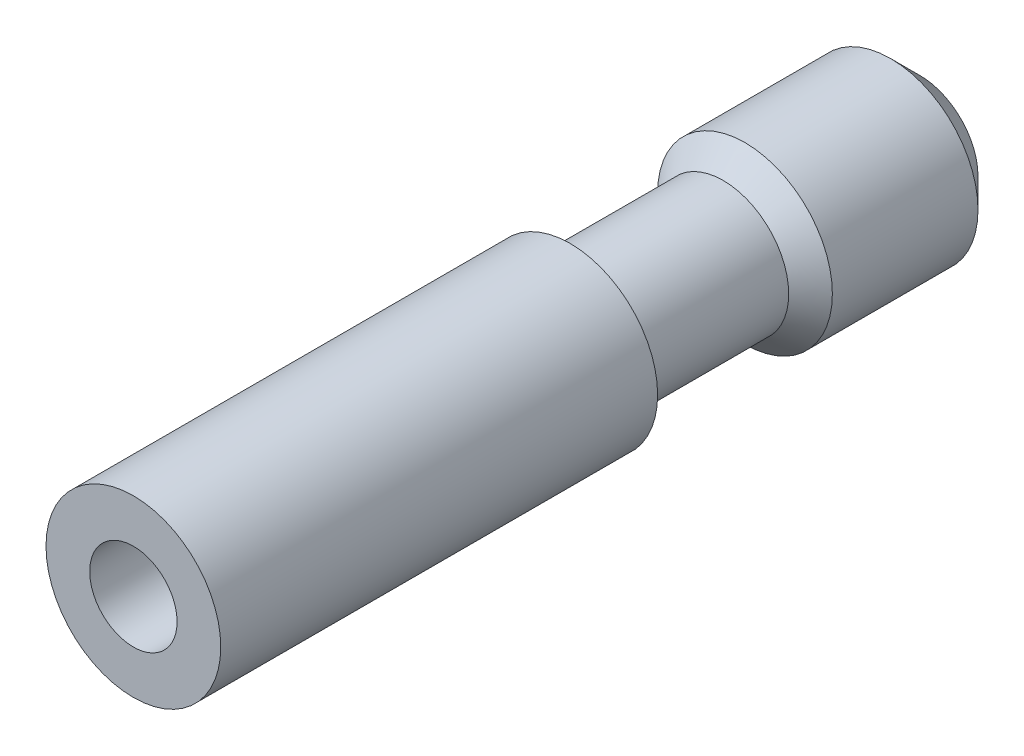
SolidWorks part; units mm, degrees
ref_plane "Plan de face" through (0, 0, 0) normal (0, 0, 1) x (1, 0, 0)
ref_plane "Plan de dessus" through (0, 0, 0) normal (0, 1, 0) x (1, 0, 0)
ref_plane "Plan de droite" through (0, 0, 0) normal (1, 0, 0) x (0, 0, -1)
sketch "Esquisse1" plane through (0, 0, 0) normal (0, 0, 1) x (1, 0, 0)
  circle A0 centre (0, 0) radius 3
  dimension "D1" = 6
extrude "Boss.-Extru.1" add sketch "Esquisse1" along normal blind 27 contours A0
cosmetic thread "Représentation de filetage1" parameters "D1"=5, "D2"=4.891
hole_wizard "Diamètre du perçage Ø3.0 (3)1" positions "Esquisse3" profile "Esquisse2" hole size "Ø3.0" standard "ISO"
sketch "Esquisse3" plane through (0, 0, 27) normal (0, 0, 1) x (1, 0, 0)
  point P0 (0, 0)
sketch "Esquisse2" plane through (0, 0, 27) normal (1, 0, 0) x (0, -1, 0)
  line L0 (0, 0) -> (0, 25.4013)
  line L1 (0, 25.4013) -> (1.5, 24.5)
  line L2 (1.5, 24.5) -> (1.5, 0)
  line L5 (1.5, 0) -> (0, 0)
  line L10 (0, 25.4013) -> (-1.5, 24.5) construction
  line L11 (0, -6.35) -> (0, 107.95) construction
  dimension "Diamètre du perçage" = 3
  dimension "Profondeur du perçage" = 24.5
  dimension "Angle de pointe" = 118
hole_wizard "Diamètre du perçage Ø2.5 (2.5)1" positions "Esquisse5" profile "Esquisse4" hole size "Ø2.5" standard "ISO"
sketch "Esquisse5" plane through (0, 0, 0) normal (0, 0, -1) x (-1, 0, 0)
  point P0 (0, 0)
sketch "Esquisse4" plane through (0, 0, 0) normal (1, 0, 0) x (0, 1, 0)
  line L0 (0, 0) -> (0, 3.7511)
  line L1 (0, 3.7511) -> (1.25, 3)
  line L2 (1.25, 3) -> (1.25, 0)
  line L5 (1.25, 0) -> (0, 0)
  line L10 (0, 3.7511) -> (-1.25, 3) construction
  line L11 (0, -6.35) -> (0, 107.95) construction
  dimension "Diamètre du perçage" = 2.5
  dimension "Profondeur du perçage" = 3
  dimension "Angle de pointe" = 118
sketch "Esquisse6" plane through (0, 0, 27) normal (0, 0, 1) x (1, 0, 0)
  line L1 (-6.0949, -5.2635) -> (5.6553, -5.2635)
  line L2 (-6.0949, -5.2635) -> (-6.0949, 6.1211)
  line L3 (-6.0949, 6.1211) -> (5.6553, 6.1211)
  line L4 (5.6553, -5.2635) -> (5.6553, 6.1211)
  circle A0 centre (0, 0) radius 2.25
  dimension "D1" = 4.5
extrude "Enlèv. mat.-Extru.1" cut sketch "Esquisse6" against normal blind 6 from offset 15 offset against normal yes
chamfer "Chanfrein1" distance 1 angle 45 1 edges at (3, 0, 0)
chamfer "Chanfrein2" distance 0.75 angle 45 1 edges at (2.25, 0, 6)
